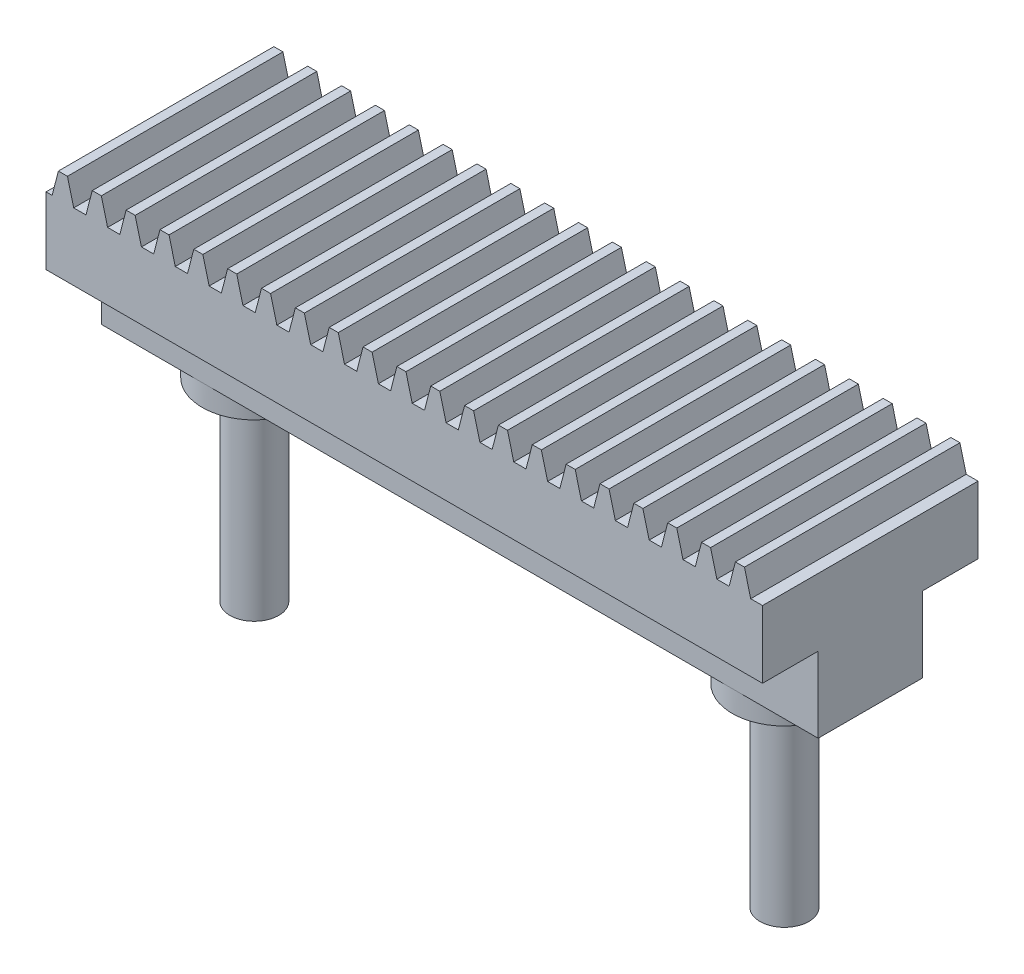
SolidWorks part; units mm, degrees
extrude "Blank" add sketch "BlankSke" against normal blind 20
sketch "BlankSke" plane through (0, 0, 0) normal (0, 0, 1) x (1, 0, 0)
  line L1 (0, 0) -> (100, 0)
  line L2 (0, 0) -> (0, 12.75)
  line L3 (0, 12.75) -> (100, 12.75)
  line L4 (100, 0) -> (100, 12.75)
  dimension "Length" = 100
ref_plane "Plane1" through (0, 0, 0) normal (0, 0, 1) x (1, 0, 0)
ref_plane "Plane2" through (0, 0, 0) normal (0, 1, 0) x (1, 0, 0)
ref_plane "Plane3" through (0, 0, 0) normal (1, 0, 0) x (0, 0, -1)
other "Configuration Table"
sketch "HoldingSke" plane through (0, 0, 0) normal (0, 1, 0) x (1, 0, 0)
  line L0 (0, 0) -> (0.0928, 0.6602)
  line L1 (-15, 0) -> (100, 0) construction
  line L2 (0, 0) -> (-2.1039, 2.3779)
  line L3 (0, 0) -> (-11.863, 4.5341)
  line L4 (0, 0) -> (7.9495, 3.3743)
  line L5 (0, 0) -> (-23.7986, -8.8762)
  line L6 (0, 0) -> (-10.5278, -7.1032)
  line L9 (-67.7845, 28.3722) -> (29.0302, 53.4102)
  line L10 (-76.2, 3.8779) -> (-64.95, 3.8779)
  line L11 (0, 0) -> (-20, 0)
  line L12 (-76.2, 101.6) -> (-76.147, 101.6)
  line L13 (24.9733, 27.94) -> (52.9518, 28.4284)
  line L14 (24.9733, 27.94) -> (24.9743, 27.94)
  line L15 (24.9733, 27.94) -> (100.4006, 29.5858)
  circle A0 centre (0, 0) radius 19.05
  circle A1 centre (0, 0) radius 5.625
  circle A2 centre (0, 0) radius 12.7
  dimension "Num_teeth" = 23
  dimension "Width" = 20
  dimension "Length" = 100
  dimension "Pitch_height" = 11.25
sketch "TooCutSkeIll" plane through (0, 0, 0) normal (0, 0, 1) x (1, 0, 0)
  line L0 (-1.7134, 12.705) -> (-0.9251, 9.6569)
  line L1 (-0.5611, 9.375) -> (0.5611, 9.375)
  line L2 (0.9251, 9.6569) -> (1.7134, 12.705)
  line L3 (100, 12.75) -> (0, 12.75) construction
  line L4 (0, 0) -> (0, 64.897) construction
  line L5 (-13.208, 11.25) -> (12.954, 11.25) construction
  line L6 (0, 0) -> (100, 0) construction
  line L7 (1.3371, 11.25) -> (1.3371, 48.7463) construction
  line L8 (-1.3371, 11.25) -> (-1.3371, 48.7463) construction
  line L9 (1.7715, 12.75) -> (1.7715, 12.7754)
  line L10 (-1.7715, 12.75) -> (-1.7715, 12.7754)
  line L11 (-1.7715, 12.7754) -> (1.7715, 12.7754)
  arc A0 (0.5611, 9.375) -> (0.9251, 9.6569) centre (0.5611, 9.751) ccw
  arc A1 (-0.9251, 9.6569) -> (-0.5611, 9.375) centre (-0.5611, 9.751) ccw
  arc A2 (1.7715, 12.75) -> (1.7134, 12.705) centre (1.7715, 12.69) ccw
  arc A3 (-1.7134, 12.705) -> (-1.7715, 12.75) centre (-1.7715, 12.69) ccw
  dimension "Addendum_plus" = 1.5254
  dimension "Pitch_height" = 11.25
  dimension "Pressure_angle" = 14.5
  dimension "Gap_width" = 2.6742
  dimension "Dedendum" = 1.875
extrude "ToothCutIll" [suppressed] cut sketch "TooCutSkeIll" against normal through all
sketch "TooCutSkeSim" plane through (0, 0, 0) normal (0, 0, 1) x (1, 0, 0)
  line L0 (0.8522, 9.375) -> (-0.8522, 9.375)
  line L1 (1.7316, 12.7754) -> (0.8522, 9.375)
  line L2 (0, 17.4625) -> (0, 53.467) construction
  line L3 (1.7316, 12.7754) -> (-1.7316, 12.7754)
  line L6 (-1.7316, 12.7754) -> (-0.8522, 9.375)
  line L9 (-1.3371, 11.25) -> (1.3371, 11.25) construction
  line L10 (0, 0) -> (100, 0) construction
  line L11 (1.3371, 11.25) -> (1.3371, 53.467) construction
  line L12 (-1.3371, 11.25) -> (-1.3371, 53.467) construction
  dimension "Addendum_plus" = 1.5254
  dimension "Pitch_height" = 11.25
  dimension "Pressure_angle" = 14.5
  dimension "Gap_width" = 2.6742
  dimension "Dedendum" = 1.875
extrude "ToothCutSim" cut sketch "TooCutSkeSim" against normal through all
pattern_linear "TeethCuts" count 23 spacing 4.7124 along (1, 0, 0) of "ToothCutIll", "ToothCutSim"
sketch "Croquis1" plane through (0, 0, 0) normal (0, 0, 1) x (1, 0, 0)
  line L89 (99.8124, 9.375) -> (98.108, 9.375)
  line L90 (98.108, 9.375) -> (97.2351, 12.75)
  line L91 (97.2351, 12.75) -> (95.9728, 12.75)
  line L92 (95.9728, 12.75) -> (95.1, 9.375)
  line L93 (95.1, 9.375) -> (93.3956, 9.375)
  line L94 (93.3956, 9.375) -> (92.5228, 12.75)
  line L95 (92.5228, 12.75) -> (91.2604, 12.75)
  line L96 (91.2604, 12.75) -> (90.3876, 9.375)
  line L97 (90.3876, 9.375) -> (88.6832, 9.375)
  line L98 (88.6832, 9.375) -> (87.8104, 12.75)
  line L99 (87.8104, 12.75) -> (86.548, 12.75)
  line L100 (86.548, 12.75) -> (85.6752, 9.375)
  line L101 (85.6752, 9.375) -> (83.9708, 9.375)
  line L102 (83.9708, 9.375) -> (83.098, 12.75)
  line L103 (83.098, 12.75) -> (81.8356, 12.75)
  line L104 (81.8356, 12.75) -> (80.9628, 9.375)
  line L105 (80.9628, 9.375) -> (79.2584, 9.375)
  line L106 (79.2584, 9.375) -> (78.3856, 12.75)
  line L107 (78.3856, 12.75) -> (77.1232, 12.75)
  line L108 (77.1232, 12.75) -> (76.2504, 9.375)
  line L109 (76.2504, 9.375) -> (74.546, 9.375)
  line L110 (74.546, 9.375) -> (73.6732, 12.75)
  line L111 (73.6732, 12.75) -> (72.4109, 12.75)
  line L112 (72.4109, 12.75) -> (71.538, 9.375)
  line L113 (71.538, 9.375) -> (69.8336, 9.375)
  line L114 (69.8336, 9.375) -> (68.9608, 12.75)
  line L115 (68.9608, 12.75) -> (67.6985, 12.75)
  line L116 (67.6985, 12.75) -> (66.8256, 9.375)
  line L117 (66.8256, 9.375) -> (65.1213, 9.375)
  line L118 (65.1213, 9.375) -> (64.2484, 12.75)
  line L119 (64.2484, 12.75) -> (62.9861, 12.75)
  line L120 (62.9861, 12.75) -> (62.1132, 9.375)
  line L121 (62.1132, 9.375) -> (60.4089, 9.375)
  line L122 (60.4089, 9.375) -> (59.536, 12.75)
  line L123 (59.536, 12.75) -> (58.2737, 12.75)
  line L124 (58.2737, 12.75) -> (57.4009, 9.375)
  line L125 (57.4009, 9.375) -> (55.6965, 9.375)
  line L126 (55.6965, 9.375) -> (54.8236, 12.75)
  line L127 (54.8236, 12.75) -> (53.5613, 12.75)
  line L128 (53.5613, 12.75) -> (52.6885, 9.375)
  line L129 (52.6885, 9.375) -> (50.9841, 9.375)
  line L130 (50.9841, 9.375) -> (50.1113, 12.75)
  line L131 (50.1113, 12.75) -> (48.8489, 12.75)
  line L132 (48.8489, 12.75) -> (47.9761, 9.375)
  line L133 (47.9761, 9.375) -> (46.2717, 9.375)
  line L134 (46.2717, 9.375) -> (45.3989, 12.75)
  line L135 (45.3989, 12.75) -> (44.1365, 12.75)
  line L136 (44.1365, 12.75) -> (43.2637, 9.375)
  line L137 (43.2637, 9.375) -> (41.5593, 9.375)
  line L138 (41.5593, 9.375) -> (40.6865, 12.75)
  line L139 (40.6865, 12.75) -> (39.4241, 12.75)
  line L140 (39.4241, 12.75) -> (38.5513, 9.375)
  line L141 (38.5513, 9.375) -> (36.8469, 9.375)
  line L142 (36.8469, 9.375) -> (35.9741, 12.75)
  line L143 (35.9741, 12.75) -> (34.7117, 12.75)
  line L144 (34.7117, 12.75) -> (33.8389, 9.375)
  line L145 (33.8389, 9.375) -> (32.1345, 9.375)
  line L146 (32.1345, 9.375) -> (31.2617, 12.75)
  line L147 (31.2617, 12.75) -> (29.9994, 12.75)
  line L148 (29.9994, 12.75) -> (29.1265, 9.375)
  line L149 (29.1265, 9.375) -> (27.4221, 9.375)
  line L150 (27.4221, 9.375) -> (26.5493, 12.75)
  line L151 (26.5493, 12.75) -> (25.287, 12.75)
  line L152 (25.287, 12.75) -> (24.4141, 9.375)
  line L153 (24.4141, 9.375) -> (22.7098, 9.375)
  line L154 (22.7098, 9.375) -> (21.8369, 12.75)
  line L155 (21.8369, 12.75) -> (20.5746, 12.75)
  line L156 (20.5746, 12.75) -> (19.7017, 9.375)
  line L157 (19.7017, 9.375) -> (17.9974, 9.375)
  line L158 (17.9974, 9.375) -> (17.1245, 12.75)
  line L159 (17.1245, 12.75) -> (15.8622, 12.75)
  line L160 (15.8622, 12.75) -> (14.9894, 9.375)
  line L161 (14.9894, 9.375) -> (13.285, 9.375)
  line L162 (13.285, 9.375) -> (12.4121, 12.75)
  line L163 (12.4121, 12.75) -> (11.1498, 12.75)
  line L164 (11.1498, 12.75) -> (10.277, 9.375)
  line L165 (10.277, 9.375) -> (8.5726, 9.375)
  line L166 (8.5726, 9.375) -> (7.6998, 12.75)
  line L167 (7.6998, 12.75) -> (6.4374, 12.75)
  line L168 (6.4374, 12.75) -> (5.5646, 9.375)
  line L169 (5.5646, 9.375) -> (3.8602, 9.375)
  line L170 (3.8602, 9.375) -> (2.9874, 12.75)
  line L171 (2.9874, 12.75) -> (1.725, 12.75)
  line L172 (1.725, 12.75) -> (0.8522, 9.375)
  line L173 (0.8522, 9.375) -> (0, 9.375)
  line L174 (0, 9.375) -> (0, 0)
  line L175 (0, 0) -> (100, 0)
  line L176 (100, 0) -> (100, 10.1006)
  line L177 (100, 10.1006) -> (99.8124, 9.375)
  line L178 (99.8124, 9.375) -> (98.108, 9.375)
  line L179 (98.108, 9.375) -> (97.2351, 12.75)
  line L180 (97.2351, 12.75) -> (95.9728, 12.75)
  line L181 (95.9728, 12.75) -> (95.1, 9.375)
  line L182 (95.1, 9.375) -> (93.3956, 9.375)
  line L183 (93.3956, 9.375) -> (92.5228, 12.75)
  line L184 (92.5228, 12.75) -> (91.2604, 12.75)
  line L185 (91.2604, 12.75) -> (90.3876, 9.375)
  line L186 (90.3876, 9.375) -> (88.6832, 9.375)
  line L187 (88.6832, 9.375) -> (87.8104, 12.75)
  line L188 (87.8104, 12.75) -> (86.548, 12.75)
  line L189 (86.548, 12.75) -> (85.6752, 9.375)
  line L190 (85.6752, 9.375) -> (83.9708, 9.375)
  line L191 (83.9708, 9.375) -> (83.098, 12.75)
  line L192 (83.098, 12.75) -> (81.8356, 12.75)
  line L193 (81.8356, 12.75) -> (80.9628, 9.375)
  line L194 (80.9628, 9.375) -> (79.2584, 9.375)
  line L195 (79.2584, 9.375) -> (78.3856, 12.75)
  line L196 (78.3856, 12.75) -> (77.1232, 12.75)
  line L197 (77.1232, 12.75) -> (76.2504, 9.375)
  line L198 (76.2504, 9.375) -> (74.546, 9.375)
  line L199 (74.546, 9.375) -> (73.6732, 12.75)
  line L200 (73.6732, 12.75) -> (72.4109, 12.75)
  line L201 (72.4109, 12.75) -> (71.538, 9.375)
  line L202 (71.538, 9.375) -> (69.8336, 9.375)
  line L203 (69.8336, 9.375) -> (68.9608, 12.75)
  line L204 (68.9608, 12.75) -> (67.6985, 12.75)
  line L205 (67.6985, 12.75) -> (66.8256, 9.375)
  line L206 (66.8256, 9.375) -> (65.1213, 9.375)
  line L207 (65.1213, 9.375) -> (64.2484, 12.75)
  line L208 (64.2484, 12.75) -> (62.9861, 12.75)
  line L209 (62.9861, 12.75) -> (62.1132, 9.375)
  line L210 (62.1132, 9.375) -> (60.4089, 9.375)
  line L211 (60.4089, 9.375) -> (59.536, 12.75)
  line L212 (59.536, 12.75) -> (58.2737, 12.75)
  line L213 (58.2737, 12.75) -> (57.4009, 9.375)
  line L214 (57.4009, 9.375) -> (55.6965, 9.375)
  line L215 (55.6965, 9.375) -> (54.8236, 12.75)
  line L216 (54.8236, 12.75) -> (53.5613, 12.75)
  line L217 (53.5613, 12.75) -> (52.6885, 9.375)
  line L218 (52.6885, 9.375) -> (50.9841, 9.375)
  line L219 (50.9841, 9.375) -> (50.1113, 12.75)
  line L220 (50.1113, 12.75) -> (48.8489, 12.75)
  line L221 (48.8489, 12.75) -> (47.9761, 9.375)
  line L222 (47.9761, 9.375) -> (46.2717, 9.375)
  line L223 (46.2717, 9.375) -> (45.3989, 12.75)
  line L224 (45.3989, 12.75) -> (44.1365, 12.75)
  line L225 (44.1365, 12.75) -> (43.2637, 9.375)
  line L226 (43.2637, 9.375) -> (41.5593, 9.375)
  line L227 (41.5593, 9.375) -> (40.6865, 12.75)
  line L228 (40.6865, 12.75) -> (39.4241, 12.75)
  line L229 (39.4241, 12.75) -> (38.5513, 9.375)
  line L230 (38.5513, 9.375) -> (36.8469, 9.375)
  line L231 (36.8469, 9.375) -> (35.9741, 12.75)
  line L232 (35.9741, 12.75) -> (34.7117, 12.75)
  line L233 (34.7117, 12.75) -> (33.8389, 9.375)
  line L234 (33.8389, 9.375) -> (32.1345, 9.375)
  line L235 (32.1345, 9.375) -> (31.2617, 12.75)
  line L236 (31.2617, 12.75) -> (29.9994, 12.75)
  line L237 (29.9994, 12.75) -> (29.1265, 9.375)
  line L238 (29.1265, 9.375) -> (27.4221, 9.375)
  line L239 (27.4221, 9.375) -> (26.5493, 12.75)
  line L240 (26.5493, 12.75) -> (25.287, 12.75)
  line L241 (25.287, 12.75) -> (24.4141, 9.375)
  line L242 (24.4141, 9.375) -> (22.7098, 9.375)
  line L243 (22.7098, 9.375) -> (21.8369, 12.75)
  line L244 (21.8369, 12.75) -> (20.5746, 12.75)
  line L245 (20.5746, 12.75) -> (19.7017, 9.375)
  line L246 (19.7017, 9.375) -> (17.9974, 9.375)
  line L247 (17.9974, 9.375) -> (17.1245, 12.75)
  line L248 (17.1245, 12.75) -> (15.8622, 12.75)
  line L249 (15.8622, 12.75) -> (14.9894, 9.375)
  line L250 (14.9894, 9.375) -> (13.285, 9.375)
  line L251 (13.285, 9.375) -> (12.4121, 12.75)
  line L252 (12.4121, 12.75) -> (11.1498, 12.75)
  line L253 (11.1498, 12.75) -> (10.277, 9.375)
  line L254 (10.277, 9.375) -> (8.5726, 9.375)
  line L255 (8.5726, 9.375) -> (7.6998, 12.75)
  line L256 (7.6998, 12.75) -> (6.4374, 12.75)
  line L257 (6.4374, 12.75) -> (5.5646, 9.375)
  line L258 (5.5646, 9.375) -> (3.8602, 9.375)
  line L259 (3.8602, 9.375) -> (2.9874, 12.75)
  line L260 (2.9874, 12.75) -> (1.725, 12.75)
  line L261 (1.725, 12.75) -> (0.8522, 9.375)
  line L262 (0.8522, 9.375) -> (0, 9.375)
  line L263 (0, 9.375) -> (0, 0)
  line L264 (0, 0) -> (100, 0)
  line L265 (100, 0) -> (100, 10.1006)
  line L266 (100, 10.1006) -> (99.8124, 9.375)
  dimension "D1" = 0
extrude "Saliente-Extruir1" add sketch "Croquis1" along normal blind 10
sketch "Croquis12" plane through (100, 0, 0) normal (1, 0, 0) x (0, 0, -1)
  line L4 (20, 10.1006) -> (-10, 10.1006)
  line L5 (-10, 10.1006) -> (-10, 0)
  line L6 (-10, 0) -> (20, 0)
  line L7 (20, 0) -> (20, 10.1006)
  line L8 (20, 10.1006) -> (-10, 10.1006)
  line L9 (-10, 10.1006) -> (-10, 0)
  line L10 (-10, 0) -> (20, 0)
  line L11 (20, 0) -> (20, 10.1006)
  dimension "D1" = 0
extrude "Cortar-Extruir1" cut sketch "Croquis12" against normal blind 0.25 and the other way through all
ref_plane "Plano1" through (0, 0, -5) normal (0, 0, 1) x (1, 0, 0)
sketch "Croquis13" plane through (0, 0, 0) normal (0, -1, 0) x (1, 0, 0)
  line L0 (0, -5) -> (107.4582, -5) construction
  line L1 (0, 2.25) -> (99.75, 2.25)
  line L2 (99.75, 10) -> (99.75, -20) construction
  line L3 (99.75, 2.25) -> (99.75, -12.25)
  line L4 (0, -20) -> (99.75, -20)
  line L5 (99.75, -20) -> (99.75, 10)
  line L6 (99.75, 10) -> (0, 10)
  line L7 (0, 10) -> (0, -20)
  line L11 (0, 10) -> (0, -20) construction
  line L12 (0, 2.25) -> (0, -12.25)
  line L13 (0, -12.25) -> (99.75, -12.25)
  point P11 (99.75, -5)
  dimension "D2" = 7.25
  dimension "D1" = 0
extrude "Saliente-Extruir6" add sketch "Croquis13" along normal blind 10.5
sketch "Croquis14" plane through (0, -10.5, 0) normal (0, -1, 0) x (1, 0, 0)
  line L0 (0, -5) -> (108.0787, -5) construction
  line L4 (0, 2.25) -> (0, -12.25)
  line L5 (0, -12.25) -> (99.75, -12.25)
  line L6 (99.75, -12.25) -> (99.75, 2.25)
  line L7 (99.75, 2.25) -> (0, 2.25)
  line L8 (0, 2.25) -> (0, -12.25) construction
  line L9 (0, -12.25) -> (99.75, -12.25) construction
  line L10 (99.75, -12.25) -> (99.75, 2.25) construction
  line L11 (99.75, 2.25) -> (0, 2.25) construction
  circle A0 centre (14, -5) radius 3.4
  circle A1 centre (87.8, -5) radius 3.4
  circle A2 centre (14, -5) radius 7.25
  circle A3 centre (87.8, -5) radius 7.25
  dimension "D2" = 6.8
  dimension "D3" = 73.8
  dimension "D4" = 14
  dimension "D1" = 0
extrude "Saliente-Extruir7" add sketch "Croquis14" along normal blind 3
sketch "Croquis15" plane through (0, -10.5, 0) normal (0, -1, 0) x (1, 0, 0)
  circle A0 centre (87.8, -5) radius 3.4 construction
  circle A1 centre (14, -5) radius 3.4 construction
  circle A2 centre (87.8, -5) radius 3.4
  circle A3 centre (14, -5) radius 3.4
extrude "Saliente-Extruir8" add sketch "Croquis15" along normal blind 30
sketch "Croquis16" plane through (0, 0, 2.25) normal (0, 0, 1) x (1, 0, 0)
  line L0 (0.926, -3) -> (118.1708, -3) construction
  line L1 (46.2, -4.6) -> (46.2, -1.4)
  line L2 (34.2, -4.6) -> (28, -4.6)
  line L3 (34.2, -4.6) -> (34.2, -1.4)
  line L4 (34.2, -1.4) -> (28, -1.4)
  line L5 (28, -4.6) -> (28, -1.4)
  line L6 (99.75, 0) -> (0, 0)
  line L7 (0, 0) -> (0, -10.5)
  line L8 (0, -10.5) -> (14, -10.5)
  line L9 (14, -10.5) -> (87.8, -10.5)
  line L10 (87.8, -10.5) -> (99.75, -10.5)
  line L11 (99.75, -10.5) -> (99.75, 0)
  line L12 (99.75, 0) -> (0, 0) construction
  line L13 (0, 0) -> (0, -10.5) construction
  line L14 (0, -10.5) -> (14, -10.5) construction
  line L15 (14, -10.5) -> (87.8, -10.5) construction
  line L16 (87.8, -10.5) -> (99.75, -10.5) construction
  line L17 (99.75, -10.5) -> (99.75, 0) construction
  line L18 (34.2, -4.6) -> (28, -1.4) construction
  line L19 (34.2, -1.4) -> (28, -4.6) construction
  line L20 (46.2, -1.4) -> (40, -1.4)
  line L21 (40, -4.6) -> (40, -1.4)
  line L22 (46.2, -4.6) -> (40, -4.6)
  line L23 (58.2, -4.6) -> (58.2, -1.4)
  line L24 (58.2, -1.4) -> (52, -1.4)
  line L25 (52, -4.6) -> (52, -1.4)
  line L26 (58.2, -4.6) -> (52, -4.6)
  line L27 (70.2, -4.6) -> (70.2, -1.4)
  line L28 (70.2, -1.4) -> (64, -1.4)
  line L29 (64, -4.6) -> (64, -1.4)
  line L30 (70.2, -4.6) -> (64, -4.6)
  line L31 (82.2, -4.6) -> (82.2, -1.4)
  line L32 (82.2, -1.4) -> (76, -1.4)
  line L33 (76, -4.6) -> (76, -1.4)
  line L34 (82.2, -4.6) -> (76, -4.6)
  line L35 (94.2, -4.6) -> (94.2, -1.4)
  line L36 (94.2, -1.4) -> (88, -1.4)
  line L37 (88, -4.6) -> (88, -1.4)
  line L38 (94.2, -4.6) -> (88, -4.6)
  point P6 (31.1, -3)
  dimension "D2" = 7.5
  dimension "D3" = 28
  dimension "D4" = 6.2
  dimension "D5" = 3.2
  dimension "D1" = 0
  dimension "D6" = 6
extrude "Cortar-Extruir2" cut sketch "Croquis16" against normal through all both and the other way through all
equation "' \"Module@HoldingSke\" = 6.35"
equation "' \"Num_teeth@HoldingSke\" = 12"
equation "' \"Ap@HoldingSke\" =  20"
equation "' \"Ap@HoldingSke\" = 20"
equation "' \"Width@HoldingSke\" = 0.25 * 25.4"
equation "' \"Show_teeth@HoldingSke\" = 500"
equation "' \"Backlash@HoldingSke\" = 0.009 * 25.4"
equation "' \"Addendum_fac@HoldingSke\" = 1.0"
equation "' \"Dedendum_fac@HoldingSke\" = 1.25"
equation "' \"Dedendum_add@HoldingSke\" = 0.00005 * 25.4"
equation "' \"Clearance_fac@HoldingSke\" = 0.25"
equation "' \"Pitch_height@HoldingSke\" = 1 * 25.4"
equation "' \"Length@HoldingSke\" = 4.71 * 25.4"
equation "\"Pitch@HoldingSke\" = 1 / \"Module@HoldingSke\""
equation "\"MPH@HoldingSke\" = \"Dedendum_fac@HoldingSke\" / \"Pitch@HoldingSke\" + 2 * \"Dedendum_add@HoldingSke\" + 0.002 * 25.4"
equation "\"MPH@HoldingSke\" = ((sgn( \"MPH@HoldingSke\" - \"Pitch_height@HoldingSke\")+1)*( \"MPH@HoldingSke\" - \"Pitch_height@HoldingSke\"))/2 + \"Pitch_height@HoldingSke\""
equation "\"Blank_height@BlankSke\" = \"Pitch_height@HoldingSke\" + \"Addendum_fac@HoldingSke\"  / \"Pitch@HoldingSke\" "
equation "\"Length@BlankSke\" =  \"Length@HoldingSke\""
equation "\"Face_width@Blank\" = \"Width@HoldingSke\""
equation "\"Pressure_angle@TooCutSkeIll\" = \"Ap@HoldingSke\""
equation "\"Addendum_plus@TooCutSkeIll\" =  \"Addendum_fac@HoldingSke\"  / \"Pitch@HoldingSke\" + 0.001 *25.4"
equation "\"Dedendum@TooCutSkeIll\" = \"Dedendum_fac@HoldingSke\"  / \"Pitch@HoldingSke\""
equation "\"Pitch_height@TooCutSkeIll\" =  \"MPH@HoldingSke\""
equation "\"Gap_width@TooCutSkeIll\" = 3.14159265 / 2 / \"Pitch@HoldingSke\" + 6 * \"Backlash@HoldingSke\""
equation "\"Pressure_angle@TooCutSkeSim\" = \"Ap@HoldingSke\""
equation "\"Addendum_plus@TooCutSkeSim\" =  \"Addendum_fac@HoldingSke\"  / \"Pitch@HoldingSke\" + 0.001 * 25.4"
equation "\"Dedendum@TooCutSkeSim\" = \"Dedendum_fac@HoldingSke\"  / \"Pitch@HoldingSke\""
equation "\"Pitch_height@TooCutSkeSim\" =  \"MPH@HoldingSke\""
equation "\"Gap_width@TooCutSkeSim\" = 3.14159265 / 2 / \"Pitch@HoldingSke\" + 6 * \"Backlash@HoldingSke\""
equation "\"Root_fillet@TooCutSkeIll\" = \"Clearance_fac@HoldingSke\" / \"Pitch@HoldingSke\" + \"Dedendum_add@HoldingSke\""
equation "\"Break_rad@TooCutSkeIll\" = 0.02 / \"Pitch@HoldingSke\" * 2"
equation "\"Linear_pitch@TeethCuts\" = 3.14159265 / \"Pitch@HoldingSke\""
equation "\"Num_teeth@HoldingSke\" = int( ( \"Length@HoldingSke\" + 0 ) / (3.14159265 / \"Pitch@HoldingSke\")) + 0.9999  + 1"
equation " \"Num_teeth@TeethCuts\" = int( \"Show_teeth@HoldingSke\" ) + 1"
equation " \"Num_teeth@TeethCuts\" = ((sgn( \"Num_teeth@TeethCuts\" - \"Num_teeth@HoldingSke\" )-1)*( \"Num_teeth@TeethCuts\" - \"Num_teeth@HoldingSke\" ))/-2+ \"Num_teeth@HoldingSke\""
equation " \"Num_teeth@TeethCuts\" = ((sgn( \"Num_teeth@TeethCuts\" - 2.0)+1)*( \"Num_teeth@TeethCuts\" - 2.0))/2 +2.0"
